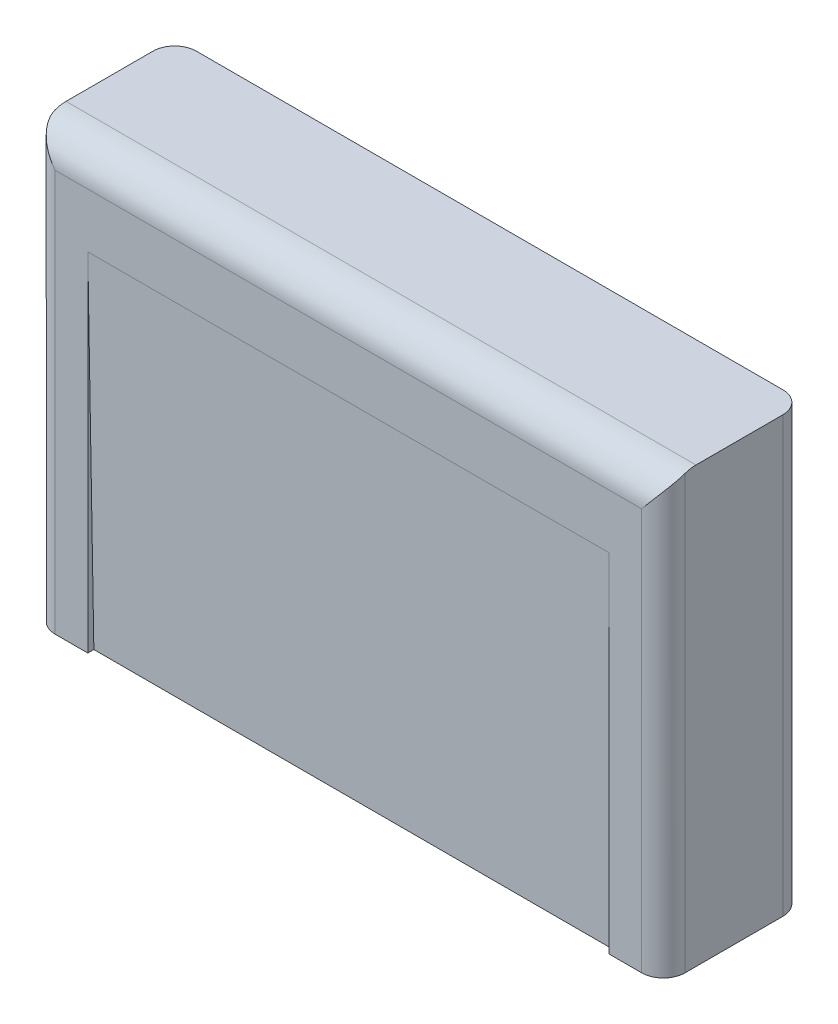
SolidWorks part; units mm, degrees
material "K110"
ref_plane "Front Plane" through (0, 0, 0) normal (0, 0, 1) x (1, 0, 0)
ref_plane "Top Plane" through (0, 0, 0) normal (0, 1, 0) x (1, 0, 0)
ref_plane "Right Plane" through (0, 0, 0) normal (1, 0, 0) x (0, 0, -1)
sketch "Sketch1" plane through (0, 0, 0) normal (0, 1, 0) x (1, 0, 0)
  line L1 (-29, -6.5) -> (29, -6.5)
  line L2 (-29, -6.5) -> (-29, 6.5)
  line L3 (-29, 6.5) -> (29, 6.5)
  line L4 (29, -6.5) -> (29, 6.5)
  line L5 (-29, -6.5) -> (29, 6.5) construction
  line L6 (-29, 6.5) -> (29, -6.5) construction
  point P0 (0, 0)
  dimension "D1" = 13
  dimension "D2" = 58
extrude "Boss-Extrude1" add sketch "Sketch1" against normal blind 40
fillet "Fillet1" radius 2 4 edges at (-29, -20, -6.5) (-29, -20, 6.5) (29, -20, -6.5) (29, -20, 6.5)
fillet "Fillet2" radius 3 1 edges at (0, 0, 6.5) tangent propagation no
hole_wizard "M6 Tapped Hole1" positions "Sketch4" profile "Sketch3" tap size "M6" standard "ISO"
sketch "Sketch4" plane through (0, -40, 0) normal (0, -1, 0) x (-1, 0, 0)
  line L0 (-29, -4.5) -> (-29, 4.5) construction
  line L1 (29, 4.5) -> (29, -4.5) construction
  point P0 (-21.5, 0)
  point P2 (21.5, 0)
  dimension "D1" = 7.5
  dimension "D2" = 7.5
sketch "Sketch3" plane through (21.5, -40, 0) normal (1, 0, 0) x (0, 0, -1)
  line L0 (0, 0) -> (0, 18.5022)
  line L1 (0, 18.5022) -> (2.5, 17)
  line L2 (2.5, 17) -> (2.5, 0.525)
  line L3 (2.5, 0.525) -> (3.025, 0)
  line L5 (3.025, 0) -> (0, 0)
  line L6 (-2.5, 0.525) -> (-3.025, 0) construction
  line L10 (0, 18.5022) -> (-2.5, 17) construction
  line L11 (0, -6.35) -> (0, 107.95) construction
  dimension "Tap Drill Dia." = 5
  dimension "Tap Drill Depth" = 17
  dimension "Near C'Sink Dia." = 6.05
  dimension "Near C'Sink Angle" = 90
  dimension "Drill Angle" = 118
cosmetic thread "Hole Thread1" parameters "D1"=12, "D2"=6
cosmetic thread "Hole Thread2" parameters "D1"=12, "D2"=6
sketch "Sketch5" plane through (0, 0, 0) normal (1, 0, 0) x (0, 0, -1)
  line L4 (-6.5, -8) -> (-5.9414, -40)
  line L5 (-6.5, -40) -> (-6.5, -3) construction
  line L6 (-6.5, -40) -> (-4.5, -40) construction
  line L7 (-5.9414, -40) -> (-6.5, -40)
  line L8 (-6.5, -40) -> (-6.5, -8)
  dimension "D1" = 5
  dimension "D2" = 1
extrude "Cut-Extrude1" cut sketch "Sketch5" against normal mid plane 48
